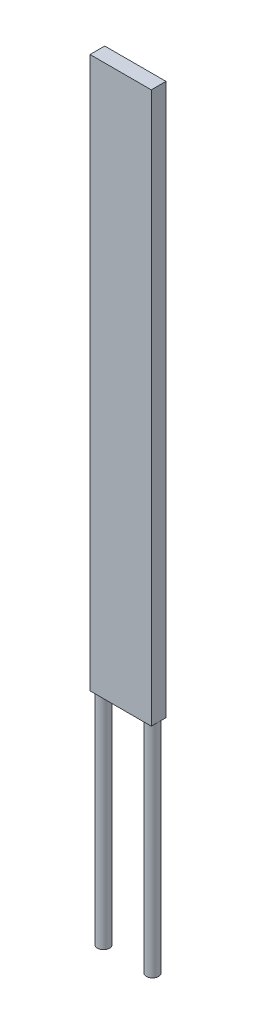
SolidWorks part; units mm, degrees
note: The reader was unsure of these and kept them because the rebuilt part matched: shared geometry of "Sketch1<3>".
ref_plane "Front Plane" through (0, 0, 0) normal (0, 0, 1) x (1, 0, 0)
ref_plane "Top Plane" through (0, 0, 0) normal (0, 1, 0) x (1, 0, 0)
ref_plane "Right Plane" through (0, 0, 0) normal (1, 0, 0) x (0, 0, -1)
sketch "Sketch1" plane through (0, 0, 0) normal (0, 0, 1) x (1, 0, 0)
  line L0 (0, 0) -> (0, 114.3)
  line L1 (0, -55) -> (0, 55) construction
  line L2 (25.4, 114.3) -> (25.4, 0)
  line L3 (55, 0) -> (-55, 0) construction
  dimension "D2" = 114.3
sweep "Sweep1" add path "Sketch1" circular profile diameter 6.35 parameters "D3"=6.35
sweep "Sweep2" add path "Sketch1<3>" circular profile diameter 6.35 parameters "D3"=6.35
sketch "Sketch1<3>" plane through (0, 0, 0) normal (0, 0, 1) x (1, 0, 0) same geometry as "Sketch1"
sketch "Sketch42" plane through (0, 0, 0) normal (0, 0, 1) x (1, 0, 0)
  line L1 (-3.175, 114.3) -> (28.575, 114.3)
  line L2 (-3.175, 114.3) -> (-3.175, 400)
  line L3 (-3.175, 400) -> (28.575, 400)
  line L4 (28.575, 114.3) -> (28.575, 400)
  dimension "D1" = 31.75
  dimension "D2" = 285.7
extrude "Boss-Extrude1" add sketch "Sketch42" along normal mid plane 7.62
